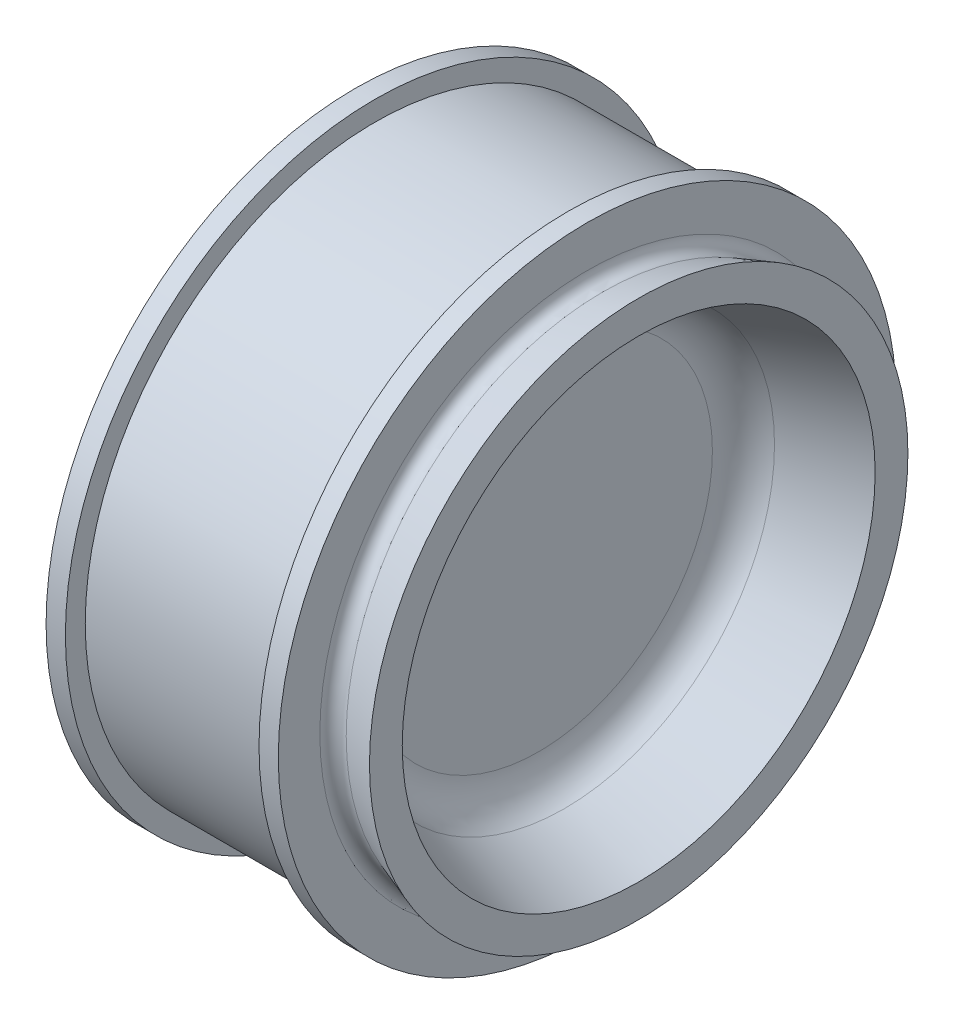
SolidWorks part; units mm, degrees
ref_plane "Plano frontal" through (0, 0, 0) normal (0, 0, 1) x (1, 0, 0)
ref_plane "Plano superior" through (0, 0, 0) normal (0, 1, 0) x (1, 0, 0)
ref_plane "Plano direito" through (0, 0, 0) normal (1, 0, 0) x (0, 0, -1)
sketch "Esboço1" plane through (0, 0, 0) normal (0, 0, 1) x (1, 0, 0)
  line L12 (30, 69.8583) -> (30, 4.8583)
  line L13 (-56.599, 4.8583) -> (122.7874, 4.8583) construction
  line L15 (30, 69.8583) -> (30, 84.8583)
  line L16 (30, 84.8583) -> (25, 84.8583)
  line L17 (25, 84.8583) -> (25, 79.8583)
  line L18 (25, 79.8583) -> (-25, 79.8583)
  line L19 (-30, 69.8583) -> (-30, 85)
  line L20 (-30, 85) -> (-25, 85)
  line L21 (-25, 85) -> (-25, 79.8583)
  line L27 (22.5, 69.8583) -> (22.5, 19.8583)
  line L28 (-30, 69.8583) -> (22.5, 69.8583)
  line L32 (0, 79.8583) -> (0, -24.4354) construction
  line L33 (22.5, 19.8583) -> (0, 19.8583)
  line L34 (0, 19.8583) -> (0, 4.8583)
  line L35 (0, 4.8583) -> (30, 4.8583)
  dimension "D2" = 5
  dimension "D3" = 15
  dimension "D4" = 80
  dimension "D5" = 15
  dimension "D6" = 22.5
  dimension "D10" = 60
  dimension "D11" = 5
  dimension "D12" = 5
revolve "Revolução2" add sketch "Esboço1" angle 360 about L13
sketch "Esboço2" plane through (0, 0, 0) normal (1, 0, 0) x (0, 0, -1)
  line L0 (-2.958, 5.3583) -> (-4.5, 5.3583)
  line L1 (-0.5, 7.8164) -> (-0.5, 9.3583)
  line L2 (0.4975, 9.3583) -> (-0.5, 9.3583)
  line L3 (0.4975, 9.3583) -> (0.4975, 7.8168)
  line L4 (2.958, 5.3583) -> (4.5, 5.3583)
  line L5 (4.5, 5.3583) -> (4.5, 4.3583)
  line L6 (4.5, 4.3583) -> (2.958, 4.3583)
  line L7 (0.5, 1.9003) -> (0.5, 0.3583)
  line L8 (0.5, 0.3583) -> (-0.5, 0.3583)
  line L9 (-0.5, 1.9003) -> (-0.5, 0.3583)
  line L10 (-4.5, 4.3583) -> (-2.958, 4.3583)
  line L11 (-4.5, 5.3583) -> (-4.5, 4.3583)
  arc A0 (-0.5, 7.8164) -> (-2.958, 5.3583) centre (0, 4.8583) ccw
  arc A1 (2.958, 5.3583) -> (0.4975, 7.8168) centre (0, 4.8583) ccw
  arc A2 (0.5, 1.9003) -> (2.958, 4.3583) centre (0, 4.8583) ccw
  arc A3 (-2.958, 4.3583) -> (-0.5, 1.9003) centre (0, 4.8583) ccw
  circle A5 centre (0, 4.8583) radius 15
extrude "Ressalto-extrusão1" add sketch "Esboço2" against normal blind 30 contours A5 | L0 L11 L10 A3 L9 L8 L7 A2 L6 L5 L4 A1 L3 L2 L1 A0
sketch "Esboço4" plane through (0, 0, 0) normal (0, 0, 1) x (1, 0, 0)
  line L0 (43.329, 4.8583) -> (-90.1134, 4.8583) construction
  line L4 (0, 59.2265) -> (0, 4.8583)
  line L8 (0, 4.8583) -> (-56.2285, 4.8583) construction
  line L9 (-56.2285, 4.8583) -> (43.329, 4.8583) construction
  line L10 (43.329, 74.5821) -> (0, 59.2265)
  line L11 (43.329, 74.5821) -> (43.329, 4.8583)
  line L12 (43.329, 4.8583) -> (0, 4.8583)
  line L13 (-90.1134, 4.8583) -> (114.3964, 4.8583) construction
revolve "Revolução3" add sketch "Esboço4" angle 360 about L13
sketch "Esboço5" plane through (0, 0, 0) normal (0, 0, 1) x (1, 0, 0)
  line L0 (43.329, 4.8583) -> (43.329, 66.0945)
  line L1 (43.329, -64.8654) -> (43.329, 74.5821) construction
  line L5 (43.329, 66.0945) -> (32.6723, 62.3179)
  line L7 (32.6723, 62.3179) -> (22.0156, 58.5412)
  line L8 (22.0156, 58.5412) -> (17.4264, 56.9148)
  line L9 (17.4264, 56.9148) -> (17.4264, 4.8583)
  line L10 (17.4264, 4.8583) -> (43.329, 4.8583)
revolve "Corte-Revolução3" cut sketch "Esboço5" angle 360 about L10
fillet "Filete1" radius 10 1 edges at (17.4264, 4.8583, 52.0565)
fillet "Filete5" radius 3 1 edges at (30, 4.8583, 65)
ref_plane "Plano1" through (-30, 0, 0) normal (-1, 0, 0) x (0, 0, 1)
sketch "Esboço7" plane through (-30, 0, 0) normal (-1, 0, 0) x (0, 0, 1)
  line L1 (-11, 4.8583) -> (-11, -5.3397)
  line L3 (-11, 4.8583) -> (-11, 15.0564)
  line L4 (-11, 15.0564) -> (-64.195, 15.0564)
  line L6 (11, 4.8583) -> (11, 15.0564)
  line L7 (11, 15.0564) -> (64.195, 15.0564)
  line L8 (11, 4.8583) -> (11, -5.3397)
  line L9 (11, -5.3397) -> (64.195, -5.3397)
  line L10 (-11, -5.3397) -> (-64.195, -5.3397)
  circle A0 centre (0, 4.8583) radius 15 construction
  arc A1 (11, -5.3397) -> (11, 15.0564) centre (0, 4.8583) ccw
  arc A5 (-11, 15.0564) -> (-11, -5.3397) centre (0, 4.8583) ccw
  circle A6 centre (0, 4.8583) radius 65 construction
  arc A7 (64.195, -5.3397) -> (64.195, 15.0564) centre (0, 4.8583) ccw
  circle A8 centre (0, 4.8583) radius 65 construction
  arc A11 (-64.195, 15.0564) -> (-64.195, -5.3397) centre (0, 4.8583) ccw
extrude "Ressalto-extrusão3" add sketch "Esboço7" against normal blind 30 contours L4 A11 L10 A5 | L9 A7 L7 A1
sketch "Esboço8" plane through (-30, 0, 0) normal (-1, 0, 0) x (0, 0, 1)
  circle A0 centre (0, 4.8583) radius 80.1417
  dimension "D1" = 160.2833
ref_plane "Plano2" through (-20.2, 0, 0) normal (-1, 0, 0) x (0, 0, 1)
sketch "Esboço9" plane through (-20.2, 0, 0) normal (-1, 0, 0) x (0, 0, 1)
  circle A0 centre (0, 4.8583) radius 3
extrude "Ressalto-extrusão4" add sketch "Esboço9" against normal blind 30
sketch "Esboço10" plane through (-20.2, 0, 0) normal (-1, 0, 0) x (0, 0, 1)
  circle A0 centre (0, 4.8583) radius 3
extrude "Ressalto-extrusão5" add sketch "Esboço10" along normal blind 2
sketch "Esboço11" plane through (0, 0, 0) normal (1, 0, 0) x (0, 0, -1)
  circle A0 centre (0, 4.8583) radius 15
  arc A1 (2.958, 5.3583) -> (0.4975, 7.8168) centre (0, 4.8583) ccw construction
  arc A2 (2.958, 5.3583) -> (0.4975, 7.8168) centre (0, 4.8583) ccw construction
ref_plane "Plano3" through (-22.2, 0, 0) normal (-1, 0, 0) x (0, 0, 1)
sketch "Esboço13" plane through (0, 0, 0) normal (0, 0, 1) x (1, 0, 0)
  line L0 (0, 0) -> (-30, 0)
  line L1 (-30, 85) -> (-30, -75.2833) construction
  line L2 (-30, 0) -> (-22.2, 0)
  line L3 (-22.2, 3.3) -> (-22.2, -3.3) construction
sketch "Esboço14" plane through (-22.2, 0, 0) normal (-1, 0, 0) x (0, 0, 1)
  circle A0 centre (0, 4.8583) radius 3
extrude "Corte-extrusão1" cut sketch "Esboço14" against normal blind 0.3
sketch "Esboço15" plane through (-21.9, 0, 0) normal (-1, 0, 0) x (0, 0, 1)
  line L3 (-0.4975, 9.3583) -> (-0.4975, 7.8168)
  line L4 (0.5, 7.8164) -> (0.5, 9.3583)
  line L5 (0.5, 9.3583) -> (-0.4975, 9.3583)
  line L6 (-0.4975, 9.3583) -> (-0.4975, 7.8168)
  line L7 (0.5, 7.8164) -> (0.5, 9.3583)
  line L8 (0.5, 9.3583) -> (-0.4975, 9.3583)
  line L9 (-4.5, 4.3583) -> (-2.958, 4.3583)
  line L10 (-2.958, 5.3583) -> (-4.5, 5.3583)
  line L11 (-4.5, 5.3583) -> (-4.5, 4.3583)
  line L12 (-4.5, 4.3583) -> (-2.958, 4.3583)
  line L13 (-2.958, 5.3583) -> (-4.5, 5.3583)
  line L14 (-4.5, 5.3583) -> (-4.5, 4.3583)
  line L15 (4.5, 5.3583) -> (2.958, 5.3583)
  line L16 (2.958, 4.3583) -> (4.5, 4.3583)
  line L17 (4.5, 4.3583) -> (4.5, 5.3583)
  line L18 (4.5, 5.3583) -> (2.958, 5.3583)
  line L19 (2.958, 4.3583) -> (4.5, 4.3583)
  line L20 (4.5, 4.3583) -> (4.5, 5.3583)
  line L21 (0.5, 0.3583) -> (0.5, 1.9003)
  line L22 (-0.5, 1.9003) -> (-0.5, 0.3583)
  line L23 (-0.5, 0.3583) -> (0.5, 0.3583)
  line L24 (0.5, 0.3583) -> (0.5, 1.9003)
  line L25 (-0.5, 1.9003) -> (-0.5, 0.3583)
  line L26 (-0.5, 0.3583) -> (0.5, 0.3583)
  circle A0 centre (0, 4.8583) radius 3
  arc A2 (0.5, 7.8164) -> (-0.4975, 7.8168) centre (0, 4.8583) ccw
  arc A3 (0.5, 7.8164) -> (-0.4975, 7.8168) centre (0, 4.8583) ccw
  arc A4 (-2.958, 5.3583) -> (-2.958, 4.3583) centre (0, 4.8583) ccw
  arc A5 (-2.958, 5.3583) -> (-2.958, 4.3583) centre (0, 4.8583) ccw
  arc A6 (2.958, 4.3583) -> (2.958, 5.3583) centre (0, 4.8583) ccw
  arc A7 (2.958, 4.3583) -> (2.958, 5.3583) centre (0, 4.8583) ccw
  arc A8 (-0.5, 1.9003) -> (0.5, 1.9003) centre (0, 4.8583) ccw
  arc A9 (-0.5, 1.9003) -> (0.5, 1.9003) centre (0, 4.8583) ccw
  arc M2 (2.958, 5.3583) -> (0.5, 7.8164) centre (0, 4.8583) ccw
  arc M3 (0.5, 7.8164) -> (-0.4975, 7.8168) centre (0, 4.8583) ccw
  arc M4 (-0.4975, 7.8168) -> (-2.958, 5.3583) centre (0, 4.8583) ccw
  arc M5 (-2.958, 5.3583) -> (-2.958, 4.3583) centre (0, 4.8583) ccw
  arc M6 (-2.958, 4.3583) -> (-0.5, 1.9003) centre (0, 4.8583) ccw
  arc M7 (-0.5, 1.9003) -> (0.5, 1.9003) centre (0, 4.8583) ccw
  arc M8 (0.5, 1.9003) -> (2.958, 4.3583) centre (0, 4.8583) ccw
  arc M9 (2.958, 4.3583) -> (2.958, 5.3583) centre (0, 4.8583) ccw
  dimension "D1" = 0
  dimension "D2" = 0
  dimension "D3" = 0
  dimension "D4" = 0
extrude "Ressalto-extrusão6" add sketch "Esboço15" against normal blind 27 contours L13 L14 L12 M5 | L7 L8 L6 M3 | L19 L20 L18 M9 | M9 M2 M3 M4 M5 M6 M7 M8 | L25 L26 L24 M7
sketch "Esboço16" plane through (-21.9, 0, 0) normal (-1, 0, 0) x (0, 0, 1)
  line L12 (0.5, 7.8164) -> (0.5, 9.3583)
  line L13 (0.5, 9.3583) -> (-0.4975, 9.3583)
  line L14 (-0.4975, 9.3583) -> (-0.4975, 7.8168)
  line L15 (-2.958, 5.3583) -> (-4.5, 5.3583)
  line L16 (-4.5, 5.3583) -> (-4.5, 4.3583)
  line L17 (-4.5, 4.3583) -> (-2.958, 4.3583)
  line L18 (-0.5, 1.9003) -> (-0.5, 0.3583)
  line L19 (-0.5, 0.3583) -> (0.5, 0.3583)
  line L20 (0.5, 0.3583) -> (0.5, 1.9003)
  line L21 (2.958, 4.3583) -> (4.5, 4.3583)
  line L22 (4.5, 4.3583) -> (4.5, 5.3583)
  line L23 (4.5, 5.3583) -> (2.958, 5.3583)
  line L24 (0.5, 7.8164) -> (0.5, 9.3583)
  line L25 (0.5, 9.3583) -> (-0.4975, 9.3583)
  line L26 (-0.4975, 9.3583) -> (-0.4975, 7.8168)
  line L27 (-2.958, 5.3583) -> (-4.5, 5.3583)
  line L28 (-4.5, 5.3583) -> (-4.5, 4.3583)
  line L29 (-4.5, 4.3583) -> (-2.958, 4.3583)
  line L30 (-0.5, 1.9003) -> (-0.5, 0.3583)
  line L31 (-0.5, 0.3583) -> (0.5, 0.3583)
  line L32 (0.5, 0.3583) -> (0.5, 1.9003)
  line L33 (2.958, 4.3583) -> (4.5, 4.3583)
  line L34 (4.5, 4.3583) -> (4.5, 5.3583)
  line L35 (4.5, 5.3583) -> (2.958, 5.3583)
  arc A4 (2.958, 5.3583) -> (0.5, 7.8164) centre (0, 4.8583) ccw
  arc A5 (-0.4975, 7.8168) -> (-2.958, 5.3583) centre (0, 4.8583) ccw
  arc A6 (-2.958, 4.3583) -> (-0.5, 1.9003) centre (0, 4.8583) ccw
  arc A7 (0.5, 1.9003) -> (2.958, 4.3583) centre (0, 4.8583) ccw
  arc A8 (2.958, 5.3583) -> (0.5, 7.8164) centre (0, 4.8583) ccw
  arc A9 (-0.4975, 7.8168) -> (-2.958, 5.3583) centre (0, 4.8583) ccw
  arc A10 (-2.958, 4.3583) -> (-0.5, 1.9003) centre (0, 4.8583) ccw
  arc A11 (0.5, 1.9003) -> (2.958, 4.3583) centre (0, 4.8583) ccw
  dimension "D1" = 0
